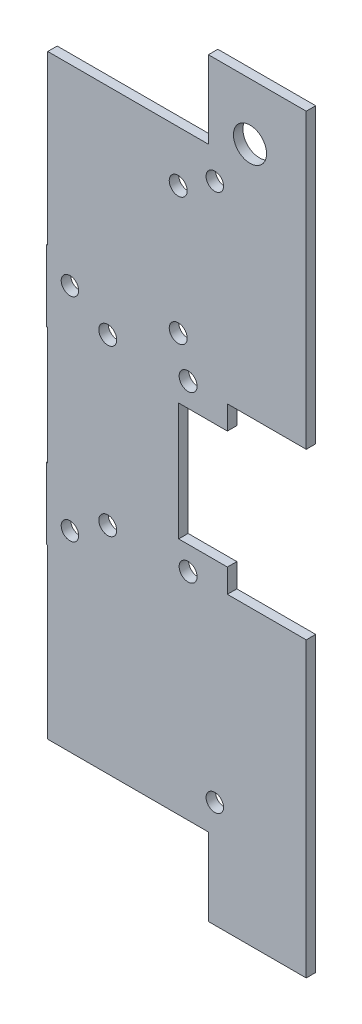
SolidWorks part; units mm, degrees
material "Thornel Mat VMA"
ref_plane "Front Plane" through (0, 0, 0) normal (0, 0, 1) x (1, 0, 0)
ref_plane "Top Plane" through (0, 0, 0) normal (0, 1, 0) x (1, 0, 0)
ref_plane "Right Plane" through (0, 0, 0) normal (1, 0, 0) x (0, 0, -1)
sketch "Sketch1" plane through (0, 0, 0) normal (0, 0, 1) x (1, 0, 0)
  line L0 (-2.9301, -104.5098) -> (-3.3149, -104.5098)
  line L1 (-3.3149, -72.8868) -> (-2.9301, -72.8868)
  line L78 (45.3299, -66.5368) -> (45.3299, -72.8868)
  line L79 (45.3299, -104.5098) -> (45.3299, -110.8598)
  line L80 (66.5174, -66.5368) -> (105.3971, 12.1397)
  line L81 (105.3971, 12.1397) -> (38.7094, 12.1397)
  line L88 (38.7094, 12.1397) -> (38.7094, -8.6883)
  line L89 (-2.9301, -8.6883) -> (38.7094, -8.6883)
  line L90 (-3.3149, -53.8368) -> (-2.9301, -53.8368)
  line L91 (-2.9301, -53.8368) -> (-2.9301, -8.6883)
  line L92 (-3.3149, -66.5368) -> (-3.3149, -53.8368)
  line L93 (-3.3149, -72.8868) -> (-3.3149, -66.5368)
  line L94 (-2.9301, -104.5098) -> (-2.9301, -72.8868)
  line L95 (-3.3149, -110.8598) -> (-3.3149, -104.5098)
  line L96 (66.5174, -110.8598) -> (105.3971, -189.5363)
  line L97 (105.3971, -189.5363) -> (38.7094, -189.5363)
  line L98 (38.7094, -189.5363) -> (38.7094, -168.7083)
  line L99 (-2.9301, -168.7083) -> (38.7094, -168.7083)
  line L106 (-3.3149, -110.8598) -> (-3.3149, -123.5598)
  line L107 (-3.3149, -123.5598) -> (-2.9301, -123.5598)
  line L108 (66.5174, -110.8598) -> (45.3299, -110.8598)
  line L109 (45.3299, -66.5368) -> (66.5174, -66.5368)
  line L110 (45.3299, -104.5098) -> (45.3299, -72.8868)
  line L111 (-2.9301, -123.5598) -> (-2.9301, -168.7083)
  circle A0 centre (90.6739, 2.6147) radius 2.3495
  circle A1 centre (41.9566, -16.4353) radius 2.3495
  circle A2 centre (3.0351, -60.1868) radius 2.3495
  circle A3 centre (3.0351, -117.2098) radius 2.3495
  circle A4 centre (41.9566, -160.9613) radius 2.3495
  circle A5 centre (90.6739, -180.0113) radius 2.3495
  circle A6 centre (51.4094, -3.1003) radius 4.445
  point P2 (90.6739, 2.6147)
  point P4 (41.9566, -16.4353)
  point P6 (3.0351, -60.1868)
  point P8 (3.0351, -117.2098)
  point P10 (41.9566, -160.9613)
  point P11 (90.6739, -180.0113)
  dimension "D2" = 4.699
  dimension "D5" = 8.89
  dimension "D1" = 66.6876
  dimension "D3" = 12.7
  dimension "D4" = 15.24
  dimension "D6" = 48.26
extrude "Boss-Extrude1" add sketch "Sketch1" along normal blind 2.54
sketch "Sketch2" plane through (0, 0, 2.54) normal (0, 0, 1) x (1, 0, 0)
  line L0 (-3.3149, -53.8368) -> (-3.3149, -72.8868) construction
  line L1 (45.3299, -66.5368) -> (66.5174, -66.5368) construction
  line L2 (45.3299, -88.6983) -> (-2.9301, -88.6983) construction
  line L3 (45.3299, -110.8598) -> (45.3299, -66.5368) construction
  line L4 (-2.9301, -72.8868) -> (-2.9301, -104.5098) construction
  circle A0 centre (13.1951, -66.5368) radius 2.413
  circle A2 centre (34.7851, -66.5368) radius 2.413
  circle A4 centre (34.7851, -110.8598) radius 2.413
  circle A6 centre (13.1951, -110.8598) radius 2.413
  dimension "D1" = 4.826
  dimension "D2" = 21.59
  dimension "D3" = 4.826
  dimension "D5" = 16.51
  dimension "D7" = 0
extrude "Cut-Extrude1" cut sketch "Sketch2" against normal through all
sketch "Sketch3" plane through (0, 0, 2.54) normal (0, 0, 1) x (1, 0, 0)
  line L0 (45.3299, -110.8598) -> (45.3299, -66.5368) construction
  line L1 (45.3299, -72.8868) -> (32.2451, -72.8868)
  line L2 (45.3299, -72.8868) -> (45.3299, -104.5098)
  line L3 (45.3299, -104.5098) -> (32.2451, -104.5098)
  line L4 (32.2451, -72.8868) -> (32.2451, -104.5098)
  line L5 (45.3299, -66.5368) -> (66.5174, -66.5368) construction
  line L6 (66.5174, -110.8598) -> (45.3299, -110.8598) construction
  circle A1 centre (13.1951, -66.5368) radius 2.413 construction
  dimension "D3" = 19.05
  dimension "D1" = 6.35
  dimension "D2" = 6.35
extrude "Cut-Extrude2" cut sketch "Sketch3" against normal through all
sketch "Sketch4" plane through (0, 0, 2.54) normal (0, 0, 1) x (1, 0, 0)
  line L0 (-2.9301, -168.7083) -> (38.7094, -168.7083) construction
  line L1 (27.4577, 15.7469) -> (40.2334, 15.7469)
  line L2 (27.4577, 15.7469) -> (27.4577, -8.6883)
  line L3 (27.4577, -8.6883) -> (40.2334, -8.6883)
  line L4 (40.2334, 15.7469) -> (40.2334, -8.6883)
  line L5 (0, -197.042) -> (40.2334, -197.042)
  line L6 (0, -197.042) -> (0, -168.7083)
  line L7 (0, -168.7083) -> (40.2334, -168.7083)
  line L8 (40.2334, -197.042) -> (40.2334, -168.7083)
  line L9 (38.7094, -168.7083) -> (38.7094, -189.5363) construction
  line L10 (38.7094, -8.6883) -> (-2.9301, -8.6883) construction
  dimension "D1" = 1.524
extrude "Cut-Extrude3" cut sketch "Sketch4" against normal through all
sketch "Sketch5" plane through (0, 0, 0) normal (0, 0, -1) x (-1, 0, 0)
  line L0 (2.9301, -8.6883) -> (2.9301, -53.8368) construction
  line L1 (-40.2334, -8.6883) -> (2.9301, -8.6883) construction
  circle A0 centre (-32.1219, -22.4043) radius 2.413
  circle A1 centre (-32.1219, -56.6943) radius 2.413
  dimension "D4" = 4.826
  dimension "D1" = 35.052
  dimension "D2" = 13.716
  dimension "D3" = 34.29
extrude "Cut-Extrude4" cut sketch "Sketch5" against normal through all
sketch "Sketch7" plane through (0, 0, 2.54) normal (0, 0, 1) x (1, 0, 0)
  line L0 (66.5174, -66.5368) -> (66.5174, 21.5221)
  line L1 (66.5174, 21.5221) -> (127.8208, 21.5221)
  line L2 (66.5174, -110.8598) -> (66.5174, -200.2563)
  line L3 (66.5174, -200.2563) -> (115.7822, -200.2563)
  line L4 (115.7822, -200.2563) -> (127.8208, 21.5221)
  line L5 (66.5174, -66.5368) -> (66.5174, -110.8598)
extrude "Cut-Extrude5" cut sketch "Sketch7" against normal through all both and the other way through all
